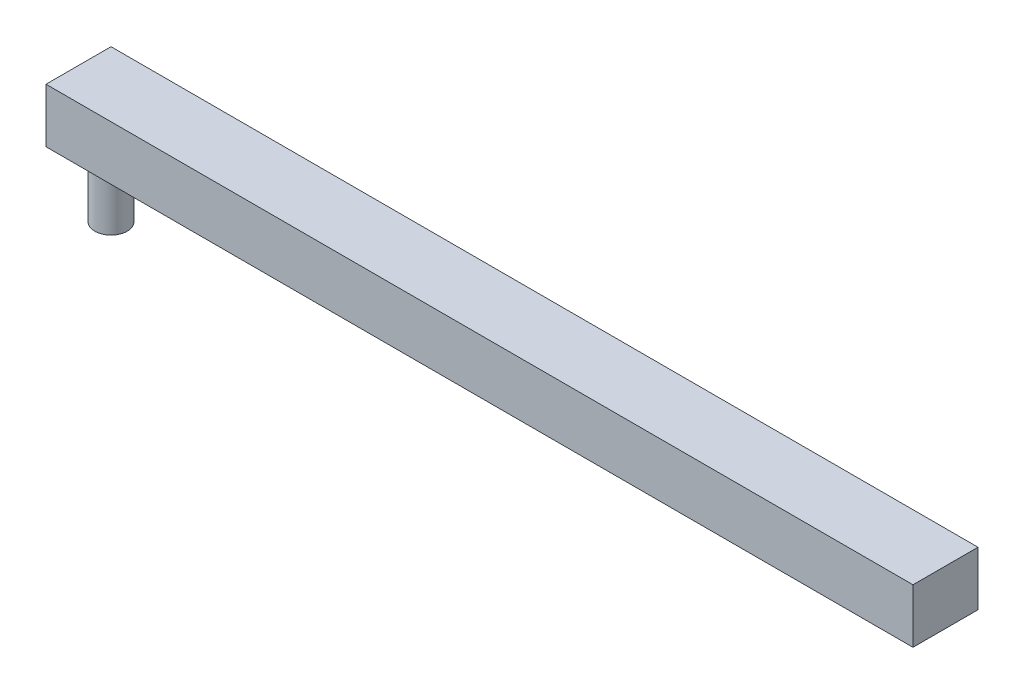
SolidWorks part; units mm, degrees
ref_plane "Front Plane" through (0, 0, 0) normal (0, 0, 1) x (1, 0, 0)
ref_plane "Top Plane" through (0, 0, 0) normal (0, 1, 0) x (1, 0, 0)
ref_plane "Right Plane" through (0, 0, 0) normal (1, 0, 0) x (0, 0, -1)
sketch "Sketch1" plane through (0, -6, 0) normal (0, 1, 0) x (1, 0, 0)
  line L0 (72.1794, 0) -> (-2.8206, 0)
  line L1 (2.1794, 0) -> (72.1794, 0) construction
  line L3 (-2.8206, 0) -> (-7.8206, 0)
  line L4 (-7.8206, 0) -> (-7.8206, 6)
  line L5 (-7.8206, 6) -> (72.1794, 6)
  line L7 (72.1794, 6) -> (72.1794, 0)
  dimension "D1" = 80
  dimension "D2" = 6
extrude "Boss-Extrude1" add sketch "Sketch1" along normal blind 5
sketch "Sketch2" plane through (0, -6, 0) normal (0, -1, 0) x (1, 0, 0)
  line L0 (-4.8206, -6) -> (-4.8206, 0) construction
  line L1 (72.1794, -6) -> (-7.8206, -6) construction
  line L2 (-7.8206, 0) -> (72.1794, 0) construction
  line L3 (-7.8206, -6) -> (-7.8206, 0) construction
  circle A0 centre (-4.8206, -3) radius 1.5
  point P4 (-4.8206, -3)
  dimension "D2" = 3
  dimension "D1" = 3
extrude "Boss-Extrude2" add sketch "Sketch2" along normal up to surface (6 mm away)
